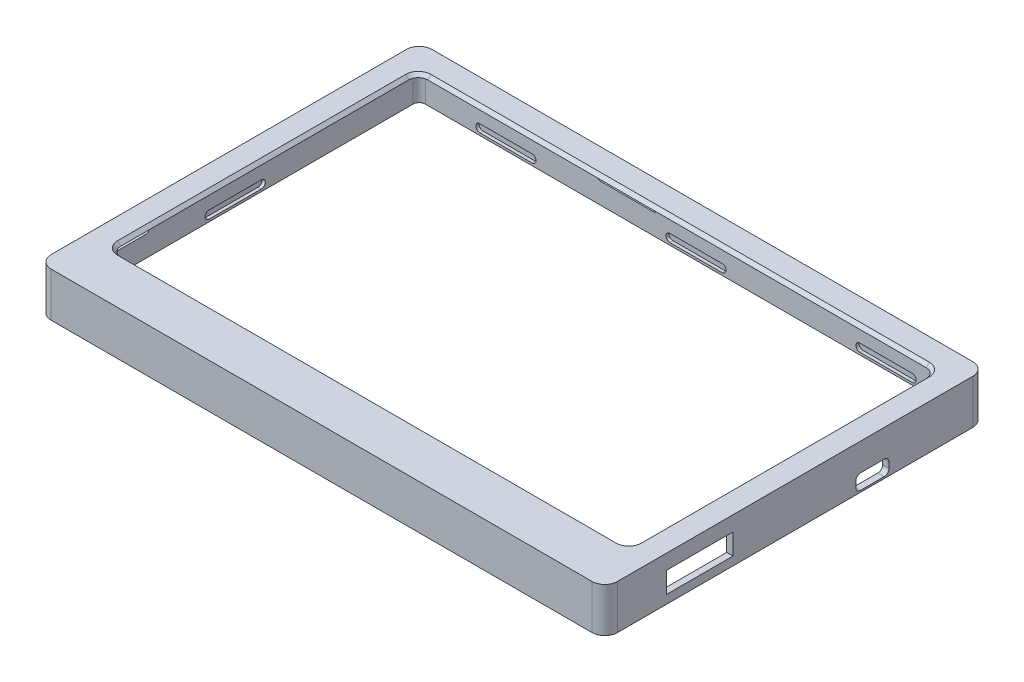
SolidWorks part; units mm, degrees
ref_plane "前基準面" through (0, 0, 0) normal (0, 0, 1) x (1, 0, 0)
ref_plane "上基準面" through (0, 0, 0) normal (0, 1, 0) x (1, 0, 0)
ref_plane "右基準面" through (0, 0, 0) normal (1, 0, 0) x (0, 0, -1)
sketch "草圖1" plane through (0, 0, 0) normal (0, 1, 0) x (1, 0, 0)
  line L1 (-89.4, 60.1) -> (89.4, 60.1)
  line L2 (-89.4, 60.1) -> (-89.4, -60.1)
  line L3 (-89.4, -60.1) -> (89.4, -60.1)
  line L4 (89.4, 60.1) -> (89.4, -60.1)
  line L5 (-89.4, 60.1) -> (89.4, -60.1) construction
  line L6 (-89.4, -60.1) -> (89.4, 60.1) construction
  point P0 (0, 0)
  dimension "D1" = 120.2
  dimension "D2" = 178.8
extrude "填料-伸長1" add sketch "草圖1" along normal blind 15
fillet "圓角1" radius 4 4 edges at (89.4, 7.5, -60.1) (89.4, 7.5, 60.1) (-89.4, 7.5, 60.1) (-89.4, 7.5, -60.1)
shell "薄殼1" thickness 2 removed face at (0, 0, 0)
sketch "草圖4" plane through (0, 15, 0) normal (0, 1, 0) x (1, 0, 0)
  line L0 (85.4, 60.1) -> (-85.4, 60.1) construction
  line L1 (-89.4107, 60.1) -> (89.4107, 60.1)
  line L2 (-89.4107, 60.1) -> (-89.4107, -60.1)
  line L3 (-89.4107, -60.1) -> (89.4107, -60.1)
  line L4 (89.4107, 60.1) -> (89.4107, -60.1)
  line L5 (-89.4107, 60.1) -> (89.4107, -60.1) construction
  line L6 (-89.4107, -60.1) -> (89.4107, 60.1) construction
  point P0 (0, 0)
  point P6 (0, 0)
extrude "除料-伸長2" cut sketch "草圖4" against normal blind 1
sketch "草圖2" plane through (0, 14, 0) normal (0, 1, 0) x (1, 0, 0)
  line L1 (-81.7, 52.1) -> (81.7, 52.1)
  line L2 (-81.7, 52.1) -> (-81.7, -44.82)
  line L3 (-81.7, -44.82) -> (81.7, -44.82)
  line L4 (81.7, 52.1) -> (81.7, -44.82)
  line L5 (-81.7, 52.1) -> (81.7, -44.82) construction
  line L6 (-81.7, -44.82) -> (81.7, 52.1) construction
  line L7 (0, 60.1) -> (0, -60.1) construction
  line L9 (85.4, 60.1) -> (-85.4, 60.1) construction
  line L10 (-85.4, -60.1) -> (85.4, -60.1) construction
  point P0 (0, 3.64)
  dimension "D1" = 8
  dimension "D2" = 163.4
  dimension "D3" = 96.92
extrude "除料-伸長1" cut sketch "草圖2" against normal up to surface (1 mm away) up to face at (0, 13, 0)
fillet "圓角2" radius 3 4 edges at (81.7, 13.5, -52.1) (81.7, 13.5, 44.82) (-81.7, 13.5, 44.82) (-81.7, 13.5, -52.1)
chamfer "導角1" distance 1 angle 45 8 edges at (0, 14, 44.82) (80.8213, 14, 43.9413) (-80.8213, 14, 43.9413) (81.7, 14, -3.64) (-81.7, 14, -3.64) (80.8213, 14, -51.2213) (-80.8213, 14, -51.2213) (0, 14, -52.1)
sketch "草圖5" plane through (0, 0, -58.1) normal (0, 0, 1) x (1, 0, 0)
  line L0 (-85.4, 14) -> (85.4, 14) construction
  line L1 (-11.85, 5.81) -> (-31.85, 5.81)
  line L2 (-11.85, 5.81) -> (-11.85, 9.81)
  line L3 (-11.85, 9.81) -> (-31.85, 9.81)
  line L4 (-31.85, 5.81) -> (-31.85, 9.81)
  line L5 (-31.85, 7.81) -> (-11.85, 7.81) construction
  line L6 (-30.1, 7.81) -> (-13.6, 7.81) construction
  line L7 (-30.1, 9.06) -> (-13.6, 9.06)
  line L8 (-30.1, 6.56) -> (-13.6, 6.56)
  arc A0 (-30.1, 9.06) -> (-30.1, 6.56) centre (-30.1, 7.81) ccw
  arc A1 (-13.6, 6.56) -> (-13.6, 9.06) centre (-13.6, 7.81) ccw
  point P12 (-21.85, 7.81)
  point P17 (-21.85, 7.1)
  point P18 (0, 0)
  dimension "D1" = 11.85
  dimension "D2" = 4.19
  dimension "D3" = 4
  dimension "D4" = 20
  dimension "D5" = 16.5
  dimension "D6" = 2.5
extrude "除料-伸長3" cut sketch "草圖5" against normal blind 1 contours L8 A1 L7 A0 | L8 A0 L7 A1 region at (-21.85, 7.81, -58.1)
sketch "草圖6" plane through (-87.4, 0, 0) normal (1, 0, 0) x (0, 0, -1)
  line L0 (-56.1, 14) -> (56.1, 14) construction
  line L1 (-26.64, 5.81) -> (-46.64, 5.81)
  line L2 (-26.64, 5.81) -> (-26.64, 9.81)
  line L3 (-26.64, 9.81) -> (-46.64, 9.81)
  line L4 (-46.64, 5.81) -> (-46.64, 9.81)
  line L5 (-26.64, 7.81) -> (-46.64, 7.81) construction
  line L6 (-28.39, 7.81) -> (-44.89, 7.81) construction
  line L7 (-28.39, 6.56) -> (-44.89, 6.56)
  line L8 (-28.39, 9.06) -> (-44.89, 9.06)
  arc A0 (-28.39, 6.56) -> (-28.39, 9.06) centre (-28.39, 7.81) ccw
  arc A1 (-44.89, 9.06) -> (-44.89, 6.56) centre (-44.89, 7.81) ccw
  point P10 (-36.64, 7.81)
  point P15 (-41.801, 7.81)
  dimension "D1" = 4.19
  dimension "D2" = 20
  dimension "D3" = 4
  dimension "D4" = 16.5
  dimension "D5" = 2.5
  dimension "D6" = 26.64
extrude "除料-伸長4" cut sketch "草圖6" against normal blind 1 contours L8 A1 L7 A0 region at (-87.4, 7.81, 36.64)
sketch "草圖7" plane through (0, 0, 58.1) normal (0, 0, -1) x (-1, 0, 0)
  line L0 (-85.4, 14) -> (85.4, 14) construction
  line L1 (-57.03, 9.81) -> (-37.03, 9.81)
  line L2 (-57.03, 9.81) -> (-57.03, 5.81)
  line L3 (-57.03, 5.81) -> (-37.03, 5.81)
  line L4 (-37.03, 9.81) -> (-37.03, 5.81)
  line L5 (-57.03, 7.81) -> (-37.03, 7.81) construction
  line L6 (-55.28, 7.81) -> (-38.78, 7.81) construction
  line L7 (-55.28, 9.06) -> (-38.78, 9.06)
  line L8 (-55.28, 6.56) -> (-38.78, 6.56)
  line L9 (0, 0) -> (0, 14) construction
  line L10 (-57.03, 9.81) -> (-37.03, 9.81)
  line L11 (-57.03, 5.81) -> (-37.03, 5.81)
  line L12 (57.03, 7.81) -> (37.03, 7.81) construction
  line L13 (57.03, 5.81) -> (37.03, 5.81)
  line L14 (57.03, 9.81) -> (37.03, 9.81)
  line L15 (37.03, 9.81) -> (37.03, 5.81)
  line L16 (57.03, 5.81) -> (37.03, 5.81)
  line L17 (57.03, 9.81) -> (57.03, 5.81)
  line L18 (57.03, 9.81) -> (37.03, 9.81)
  line L19 (55.28, 7.81) -> (38.78, 7.81) construction
  line L20 (55.28, 9.06) -> (38.78, 9.06)
  line L21 (55.28, 6.56) -> (38.78, 6.56)
  arc A0 (-55.28, 9.06) -> (-55.28, 6.56) centre (-55.28, 7.81) ccw
  arc A1 (-38.78, 6.56) -> (-38.78, 9.06) centre (-38.78, 7.81) ccw
  arc A2 (55.28, 9.06) -> (55.28, 6.56) centre (55.28, 7.81) cw
  arc A3 (38.78, 6.56) -> (38.78, 9.06) centre (38.78, 7.81) cw
  point P4 (-37.03, 7.81)
  point P12 (-47.03, 7.81)
  point P27 (47.03, 7.81)
  dimension "D1" = 20
  dimension "D2" = 4
  dimension "D3" = 37.03
  dimension "D4" = 4.19
  dimension "D5" = 16.5
  dimension "D6" = 2.5
extrude "除料-伸長5" cut sketch "草圖7" against normal blind 1 contours L8 A1 L7 A0 | A3 L21 A2 L20 region at (47.03, 7.81, 58.1) region at (-47.03, 7.81, 58.1)
sketch "草圖8" plane through (87.4, 0, 0) normal (-1, 0, 0) x (0, 0, 1)
  line L0 (-56.1, 14) -> (56.1, 14) construction
  line L1 (43.6, 5.81) -> (53.6, 5.81)
  line L2 (43.6, 5.81) -> (43.6, 9.81)
  line L3 (43.6, 9.81) -> (53.6, 9.81)
  line L4 (53.6, 5.81) -> (53.6, 9.81)
  line L5 (60.1, 14) -> (60.1, 0) construction
  line L6 (43.6, 7.81) -> (53.6, 7.81) construction
  line L7 (44.85, 7.81) -> (52.35, 7.81) construction
  line L8 (44.85, 9.06) -> (52.35, 9.06)
  line L9 (44.85, 6.56) -> (52.35, 6.56)
  arc A0 (44.85, 9.06) -> (44.85, 6.56) centre (44.85, 7.81) ccw
  arc A1 (52.35, 6.56) -> (52.35, 9.06) centre (52.35, 7.81) ccw
  point P12 (48.6, 7.81)
  point P17 (0, 0)
  point P18 (48.6, 7.81)
  dimension "D1" = 10
  dimension "D2" = 4
  dimension "D3" = 4.19
  dimension "D4" = 6.5
  dimension "D5" = 2.5
  dimension "D6" = 7.5
extrude "除料-伸長6" cut sketch "草圖8" against normal blind 1 contours A1 L8 A0 L9 region at (87.4, 7.81, 48.6)
sketch "草圖9" plane through (89.4, 0, 0) normal (1, 0, 0) x (0, 0, -1)
  line L1 (28.13, 0.54) -> (20.65, 0.54)
  line L2 (29.63, 2.04) -> (29.63, 3.82)
  line L3 (28.13, 5.32) -> (20.65, 5.32)
  line L4 (19.15, 2.04) -> (19.15, 3.82)
  line L5 (29.63, 0.54) -> (19.15, 5.32) construction
  line L6 (29.63, 5.32) -> (19.15, 0.54) construction
  line L8 (60.1, 14) -> (60.1, 0) construction
  line L9 (-56.1, 14) -> (56.1, 14) construction
  arc A0 (20.65, 5.32) -> (19.15, 3.82) centre (20.65, 3.82) ccw
  arc A1 (20.65, 0.54) -> (19.15, 2.04) centre (20.65, 2.04) cw
  arc A2 (28.13, 0.54) -> (29.63, 2.04) centre (28.13, 2.04) ccw
  arc A3 (29.63, 3.82) -> (28.13, 5.32) centre (28.13, 3.82) ccw
  point P0 (24.39, 2.93)
  dimension "D5" = 1.5
  dimension "D1" = 35.71
  dimension "D2" = 11.07
  dimension "D3" = 10.48
  dimension "D4" = 4.78
extrude "除料-伸長7" cut sketch "草圖9" against normal up to next
sketch "草圖10" plane through (89.4, 0, 0) normal (1, 0, 0) x (0, 0, -1)
  line L0 (-60.1, 0) -> (-60.1, 14) construction
  line L1 (-40.6, 9.3) -> (-19.6, 9.3)
  line L2 (-40.6, 9.3) -> (-40.6, 2.7)
  line L3 (-40.6, 2.7) -> (-19.6, 2.7)
  line L4 (-19.6, 9.3) -> (-19.6, 2.7)
  line L5 (-40.6, 9.3) -> (-19.6, 2.7) construction
  line L6 (-40.6, 2.7) -> (-19.6, 9.3) construction
  line L7 (-56.1, 14) -> (56.1, 14) construction
  point P0 (-30.1, 6)
  point P5 (-21.5446, 5.4621)
  dimension "D1" = 21
  dimension "D2" = 6.6
  dimension "D3" = 19.5
  dimension "D4" = 4.7
extrude "除料-伸長8" cut sketch "草圖10" against normal up to next
sketch "草圖11" plane through (0, 0, -58.1) normal (0, 0, 1) x (1, 0, 0)
  line L0 (-8.25, 2) -> (8.25, 2) construction
  line L1 (-8.25, 3.25) -> (8.25, 3.25)
  line L2 (-8.25, 0.75) -> (8.25, 0.75)
  line L3 (-85.4, 0) -> (85.4, 0) construction
  line L4 (51.75, 2) -> (68.25, 2) construction
  line L5 (51.75, 3.25) -> (68.25, 3.25)
  line L6 (51.75, 0.75) -> (68.25, 0.75)
  line L7 (-68.25, 2) -> (-51.75, 2) construction
  line L8 (-68.25, 3.25) -> (-51.75, 3.25)
  line L9 (-68.25, 0.75) -> (-51.75, 0.75)
  arc A0 (-8.25, 3.25) -> (-8.25, 0.75) centre (-8.25, 2) ccw
  arc A1 (8.25, 0.75) -> (8.25, 3.25) centre (8.25, 2) ccw
  arc A2 (51.75, 3.25) -> (51.75, 0.75) centre (51.75, 2) ccw
  arc A3 (68.25, 0.75) -> (68.25, 3.25) centre (68.25, 2) ccw
  arc A4 (-68.25, 3.25) -> (-68.25, 0.75) centre (-68.25, 2) ccw
  arc A5 (-51.75, 0.75) -> (-51.75, 3.25) centre (-51.75, 2) ccw
  point P2 (0, 2)
  point P13 (60, 2)
  point P20 (-60, 2)
  dimension "D1" = 16.5
  dimension "D2" = 2.5
  dimension "D3" = 2
  dimension "D4" = 2
  dimension "D5" = 2
extrude "除料-伸長9" cut sketch "草圖11" against normal blind 1
ref_plane "平面1" through (0, 0, 0) normal (0, 0, 1) x (1, 0, 0)
mirror "鏡射1" about plane through (0, 0, 0) normal (0, 0, 1) of "除料-伸長9"
ref_plane "平面2" through (0, 0, 0) normal (-1, 0, 0) x (0, 0, 1)
sketch "草圖12" plane through (-87.4, 0, 0) normal (1, 0, 0) x (0, 0, -1)
  line L0 (-8.25, 2) -> (8.25, 2) construction
  line L1 (-8.25, 3.25) -> (8.25, 3.25)
  line L2 (-8.25, 0.75) -> (8.25, 0.75)
  line L3 (-56.1, 0) -> (56.1, 0) construction
  arc A0 (-8.25, 3.25) -> (-8.25, 0.75) centre (-8.25, 2) ccw
  arc A1 (8.25, 0.75) -> (8.25, 3.25) centre (8.25, 2) ccw
  point P2 (0, 2)
  point P7 (0, 0)
  dimension "D1" = 16.5
  dimension "D2" = 2.5
  dimension "D3" = 2
extrude "除料-伸長10" cut sketch "草圖12" against normal blind 1
mirror "鏡射2" about plane through (0, 0, 0) normal (-1, 0, 0) of "除料-伸長10"
equation "\"ㄉ\"=4"
